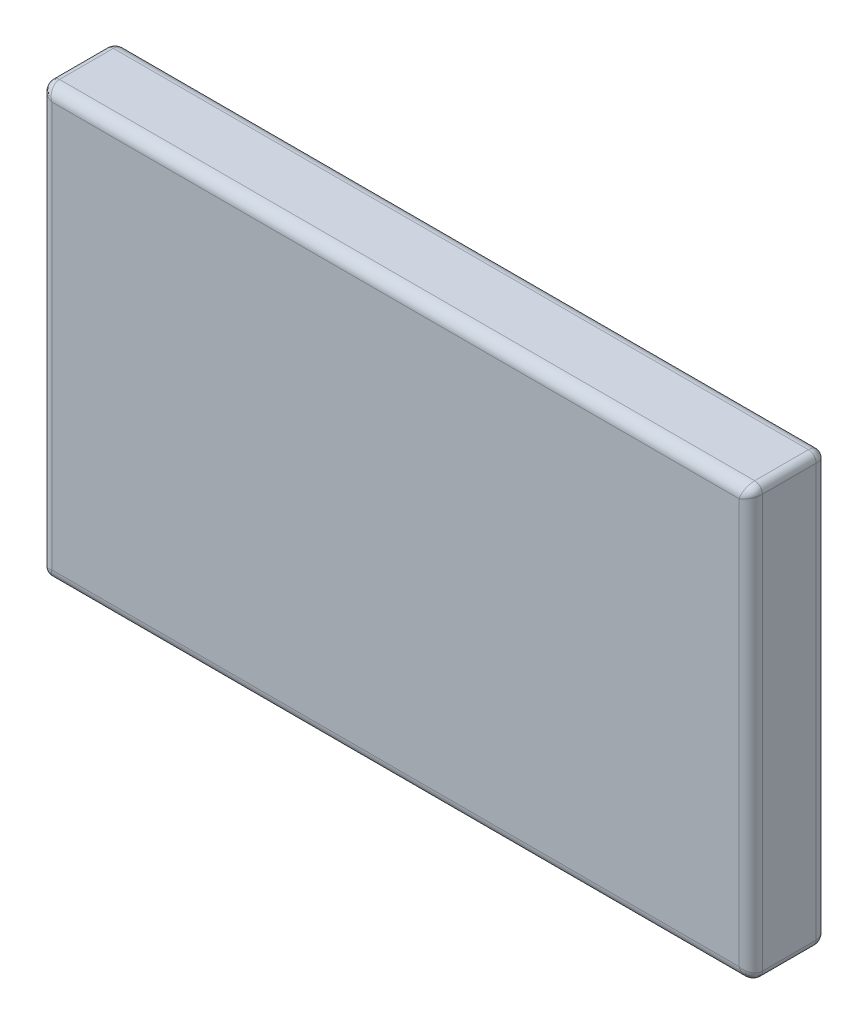
SolidWorks part; units mm, degrees
material "Cobalt"
ref_plane "Front Plane" through (0, 0, 0) normal (0, 0, 1) x (1, 0, 0)
ref_plane "Top Plane" through (0, 0, 0) normal (0, 1, 0) x (1, 0, 0)
ref_plane "Right Plane" through (0, 0, 0) normal (1, 0, 0) x (0, 0, -1)
sketch "Sketch1" plane through (0, 0, 0) normal (0, 0, 1) x (1, 0, 0)
  line L1 (-5.7912, -3.4925) -> (5.7912, -3.4925)
  line L2 (-5.7912, -3.4925) -> (-5.7912, 3.4925)
  line L3 (-5.7912, 3.4925) -> (5.7912, 3.4925)
  line L4 (5.7912, -3.4925) -> (5.7912, 3.4925)
  line L5 (-5.7912, -3.4925) -> (5.7912, 3.4925) construction
  line L6 (-5.7912, 3.4925) -> (5.7912, -3.4925) construction
  point P0 (0, 0)
  dimension "D1" = 11.5824
  dimension "D2" = 6.985
extrude "Boss-Extrude1" add sketch "Sketch1" along normal mid plane 1.2573
fillet "Fillet1" radius 0.127 4 edges at (-5.7912, -3.4925, 0) (-5.7912, 3.4925, 0) (5.7912, -3.4925, 0) (5.7912, 3.4925, 0)
fillet "Fillet2" radius 0.1905 16 edges at (5.754, -3.4553, -0.6287) (5.7912, 0, -0.6287) (5.754, 3.4553, -0.6287) (0, 3.4925, -0.6287) (-5.754, 3.4553, -0.6287) (-5.7912, 0, -0.6287) (-5.754, -3.4553, -0.6287) (0, -3.4925, -0.6287) (-5.754, 3.4553, 0.6287) (0, 3.4925, 0.6287) (5.754, 3.4553, 0.6287) (5.7912, 0, 0.6287) (5.754, -3.4553, 0.6287) (0, -3.4925, 0.6287) (-5.754, -3.4553, 0.6287) (-5.7912, 0, 0.6287)
